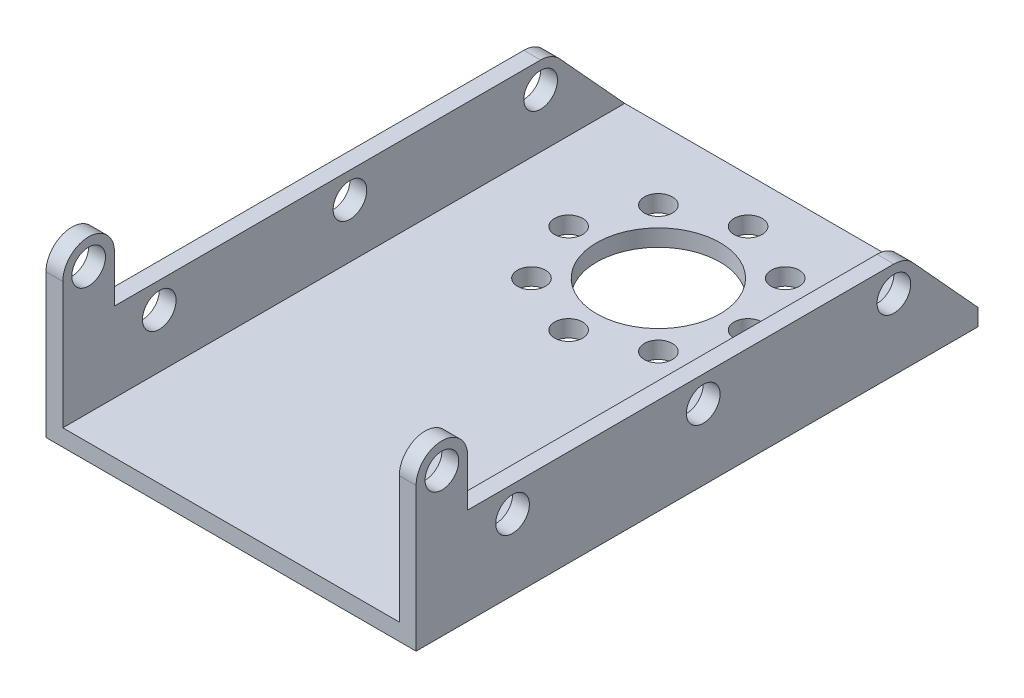
SolidWorks part; units mm, degrees
ref_plane "Front Plane" through (0, 0, 0) normal (0, 0, 1) x (1, 0, 0)
ref_plane "Top Plane" through (0, 0, 0) normal (0, 1, 0) x (1, 0, 0)
ref_plane "Right Plane" through (0, 0, 0) normal (1, 0, 0) x (0, 0, -1)
sketch "Sketch2" plane through (0, 0, 0) normal (0, 1, 0) x (1, 0, 0)
  line L0 (-15, 0) -> (15, 0) construction
  line L1 (-15, 17) -> (15, 17) construction
  line L2 (-15, 17) -> (-15, -17) construction
  line L3 (-15, -17) -> (15, -17) construction
  line L4 (15, 17) -> (15, -17) construction
  line L5 (-8.5, -23.3) -> (8.5, -23.3) construction
  line L6 (0, 17) -> (0, -0.2732) construction
  line L8 (-17.8, -26.1) -> (17.8, -26.1) construction
  line L9 (-17.8, -26.1) -> (-17.8, 24.5) construction
  line L11 (17.8, -26.1) -> (17.8, 24.5) construction
  line L12 (-12.2, 24.5) -> (12.2, 24.5) construction
  line L13 (-12.2, 24.5) -> (-12.2, -20.5) construction
  line L14 (-12.2, -20.5) -> (12.2, -20.5) construction
  line L15 (12.2, 24.5) -> (12.2, -20.5) construction
  line L20 (-12.2, 24.5) -> (-17.8, 24.5) construction
  line L21 (12.2, 24.5) -> (17.8, 24.5) construction
  line L32 (-15, 24.5) -> (15, 24.5)
  line L37 (15, 24.5) -> (15, -25.6)
  line L38 (15, -25.6) -> (-15, -25.6)
  line L39 (-15, -25.6) -> (-15, 24.5)
  circle A0 centre (0, 12.5) radius 11 construction
  circle A1 centre (-15, 17) radius 1.25 construction
  circle A2 centre (-15, 0) radius 1.25 construction
  circle A3 centre (-15, -17) radius 1.25 construction
  circle A4 centre (15, 17) radius 1.25 construction
  circle A5 centre (15, 0) radius 1.25 construction
  circle A6 centre (15, -17) radius 1.25 construction
  circle A7 centre (-8.5, -23.3) radius 1.25 construction
  circle A8 centre (8.5, -23.3) radius 1.25 construction
  circle A9 centre (0, 12.5) radius 8 construction
  circle A10 centre (-8, 12.5) radius 1.25
  circle A11 centre (-5.6569, 18.1569) radius 1.25
  circle A12 centre (0, 20.5) radius 1.25
  circle A13 centre (5.6569, 18.1569) radius 1.25
  circle A14 centre (8, 12.5) radius 1.25
  circle A15 centre (5.6569, 6.8431) radius 1.25
  circle A16 centre (0, 4.5) radius 1.25
  circle A17 centre (-5.6569, 6.8431) radius 1.25
  circle A18 centre (0, 12.5) radius 5.5
  point P6 (0, 0)
  point P11 (0, -23.3)
  point P19 (0, -26.1)
  point P24 (0, -20.5)
  point P41 (0, 24.5)
  point P59 (0, 12.5)
  dimension "D3" = 22
  dimension "D12" = 2.5
  dimension "D13" = 16
  dimension "D15" = 2.5
  dimension "D17" = 11
  dimension "D1" = 17
  dimension "D2" = 30
  dimension "D4" = 4.5
  dimension "D5" = 35.8
  dimension "D6" = 17
  dimension "D7" = 50.6
  dimension "D8" = 35.6
  dimension "D9" = 12
  dimension "D10" = 24.4
  dimension "D11" = 33
  dimension "D14" = 30
  dimension "D18" = 50.1
  dimension "D16" = 8
extrude "Boss-Extrude1" add sketch "Sketch2" along normal blind 1.5
sketch "Sketch3" plane through (0, 0, 0) normal (1, 0, 0) x (0, 0, -1)
  line L0 (-26.1, 21.3) -> (24.5, 21.3) construction
  line L9 (-26.1, 39.1) -> (24.5, 39.1) construction
  line L10 (-26.1, 39.1) -> (-26.1, 3.5) construction
  line L14 (-26.1, 3.5) -> (24.5, 3.5) construction
  line L26 (24.5, 39.1) -> (24.5, 3.5) construction
  line L27 (-20.5, 33.5) -> (24.5, 33.5) construction
  line L28 (-20.5, 33.5) -> (-20.5, 9.1) construction
  line L29 (-20.5, 9.1) -> (24.5, 9.1) construction
  line L30 (24.5, 33.5) -> (24.5, 9.1) construction
  line L31 (0, 36.3) -> (0, 6.3) construction
  line L32 (-17, 36.3) -> (17, 36.3) construction
  line L33 (-17, 36.3) -> (-17, 6.3) construction
  line L34 (-17, 6.3) -> (17, 6.3) construction
  line L35 (17, 36.3) -> (17, 6.3) construction
  line L36 (-23.3, 29.8) -> (-23.3, 12.8) construction
  line L37 (-25.6, 1.5) -> (24.5, 1.5) construction
  line L38 (0, 0) -> (25.6327, 0) construction
  line L39 (24.5, 1.5) -> (18.6981, 7.8512)
  line L40 (-23.3, 12.8) -> (-21, 12.8) construction
  line L41 (-25.6, 12.8) -> (-25.6, 1.5)
  line L42 (-17, 6.3) -> (-17, 8.6) construction
  line L43 (-21, 8.6) -> (17, 8.6)
  line L44 (-21, 12.8) -> (-21, 8.6)
  line L45 (17, 6.3) -> (17, 8.6) construction
  line L46 (-25.6, 1.5) -> (24.5, 1.5) construction
  line L47 (-25.6, 1.5) -> (-25.6, 0)
  line L48 (-25.6, 0) -> (24.5, 0)
  line L49 (24.5, 0) -> (24.5, 1.5)
  circle A36 centre (12.5, 21.3) radius 11 construction
  circle A40 centre (-23.3, 12.8) radius 2.3 construction
  arc A41 (-25.6, 12.8) -> (-21, 12.8) centre (-23.3, 12.8) cw
  circle A42 centre (17, 6.3) radius 2.3 construction
  arc A43 (17, 8.6) -> (18.6981, 7.8512) centre (17, 6.3) cw
  circle A44 centre (-23.3, 12.8) radius 1.5
  circle A45 centre (-17, 6.3) radius 1.5
  circle A46 centre (0, 6.3) radius 1.5
  circle A47 centre (17, 6.3) radius 1.5
  point P12 (-20.5, 21.3)
  point P21 (-23.3, 21.3)
  point P23 (0, 21.3)
  dimension "D3" = 33
  dimension "D12" = 2
  dimension "D14" = 0.5
  dimension "D1" = 22
  dimension "D13" = 3
  dimension "D2" = 12
  dimension "D4" = 24.4
  dimension "D5" = 35.6
  dimension "D6" = 17
  dimension "D7" = 4.5
  dimension "D8" = 17
  dimension "D9" = 50.6
  dimension "D10" = 30
  dimension "D11" = 35.8
extrude "Boss-Extrude2" add sketch "Sketch3" along normal blind 1.5 from surface starting at face at (15, 0.75, 0.55)
extrude "Boss-Extrude3" add sketch "Sketch3<2>" against normal blind 1.5 from surface starting at face at (-15, 0.75, 0.55)
sketch "Sketch3<2>" plane through (0, 0, 0) normal (1, 0, 0) x (0, 0, -1) same geometry as "Sketch3"
